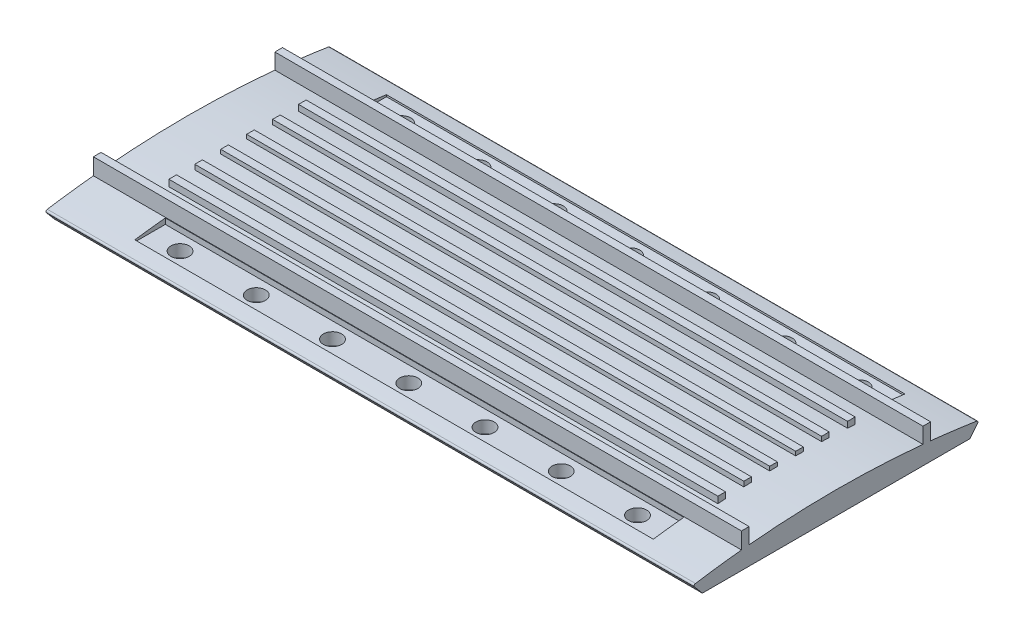
SolidWorks part; units mm, degrees
material "1060 Alloy"
ref_plane "Front Plane" through (0, 0, 0) normal (0, 0, 1) x (1, 0, 0)
ref_plane "Top Plane" through (0, 0, 0) normal (0, 1, 0) x (1, 0, 0)
ref_plane "Right Plane" through (0, 0, 0) normal (1, 0, 0) x (0, 0, -1)
sketch "Sketch1" plane through (0, 0, 0) normal (1, 0, 0) x (0, 0, -1)
  line L0 (-87.6812, 172.5341) -> (-172.5341, 87.6812)
  line L3 (-100, -20) -> (100, -20)
  line L6 (172.5341, 87.6812) -> (87.6812, 172.5341)
  line L10 (0, 0) -> (0, 98.5268) construction
  line L11 (-130.1076, 130.1076) -> (0, 0) construction
  line L12 (0, 0) -> (130.1076, 130.1076) construction
  line L17 (87.6812, 172.5341) -> (-87.6812, 172.5341) construction
  line L18 (172.5341, 87.6812) -> (100, 26.8179)
  line L19 (100, 26.8179) -> (100, -20)
  line L20 (-100, 26.8179) -> (-100, -20)
  line L21 (-172.5341, 87.6812) -> (-100, 26.8179)
  line L22 (-87.6812, 172.5341) -> (-26.8179, 100)
  line L23 (-26.8179, 100) -> (26.8179, 100)
  line L24 (26.8179, 100) -> (87.6812, 172.5341)
  line L25 (-100, 26.8179) -> (-26.8179, 100) construction
  circle A0 centre (0, 0) radius 16
  point P24 (0, 100)
  dimension "D8" = 32
  dimension "D9" = 5
  dimension "D1" = 90
  dimension "D2" = 45
  dimension "D3" = 120
  dimension "D4" = 200
  dimension "D5" = 20
  dimension "D6" = 184
  dimension "D7" = 5
sketch "Sketch2" plane through (0, 0, 0) normal (1, 0, 0) x (0, 0, -1)
  line L0 (-87.6812, 172.5341) -> (-93.9745, 180.0341)
  line L1 (-93.9745, 180.0341) -> (93.9745, 180.0341) construction
  line L2 (93.9745, 180.0341) -> (87.6812, 172.5341)
  line L3 (26.8179, 100) -> (87.6812, 172.5341) construction
  line L4 (87.6812, 172.5341) -> (-87.6812, 172.5341) construction
  line L5 (-87.6812, 172.5341) -> (-26.8179, 100) construction
  line L6 (-87.6812, 172.5341) -> (87.6812, 172.5341)
  arc A0 (-93.9745, 180.0341) -> (93.9745, 180.0341) centre (0, -412.5609) cw
  dimension "D2" = 600
  dimension "D1" = 7.5
extrude "Boss-Extrude1" add sketch "Sketch2" along normal blind 212.5 and the other way blind 212.5
sketch "Sketch3" plane through (0, 0, 0) normal (0, 1, 0) x (1, 0, 0)
  line L0 (-212.5, -87.6812) -> (-212.5, 87.6812) construction
  line L1 (-212.5, 87.6812) -> (212.5, 87.6812) construction
  circle A0 centre (-145, 72.6812) radius 6
  circle A1 centre (-95, 72.6812) radius 6
  circle A2 centre (-45, 72.6812) radius 6
  circle A3 centre (5, 72.6812) radius 6
  circle A4 centre (55, 72.6812) radius 6
  circle A5 centre (105, 72.6812) radius 6
  circle A6 centre (155, 72.6812) radius 6
  dimension "D4" = 50
  dimension "D5" = 50
  dimension "D6" = 50
  dimension "D7" = 50
  dimension "D8" = 50
  dimension "D9" = 12
  dimension "D1" = 67.5
  dimension "D2" = 15
  dimension "D3" = 50
extrude "Cut-Extrude1" cut sketch "Sketch3" along normal through all
mirror "Mirror1" about plane through (0, 0, 0) normal (0, 0, 1) of "Cut-Extrude1"
fillet "Fillet1" radius 1 2 edges at (0, 180.0341, -93.9745) (0, 180.0341, 93.9745)
sketch "Sketch4" plane through (0, 0, 0) normal (1, 0, 0) x (0, 0, -1)
  line L0 (-62, 172.5341) -> (-62, 160.5341)
  line L1 (-87.6812, 172.5341) -> (87.6812, 172.5341) construction
  line L2 (-62, 160.5341) -> (-57, 160.5341)
  line L3 (-57, 160.5341) -> (-57, 172.5341)
  line L4 (0, 0) -> (0, 248.1836) construction
  line L5 (87.6812, 172.5341) -> (-87.6812, 172.5341) construction
  line L6 (-45, 172.5341) -> (-40, 172.5341)
  line L7 (-45, 172.5341) -> (-45, 142.5341)
  line L8 (-45, 142.5341) -> (-40, 142.5341)
  line L9 (-40, 172.5341) -> (-40, 142.5341)
  line L10 (-62, 172.5341) -> (-57, 172.5341)
  line L11 (-28, 172.5341) -> (-23, 172.5341)
  line L12 (-28, 172.5341) -> (-28, 127.5341)
  line L13 (-28, 127.5341) -> (-23, 127.5341)
  line L14 (-23, 172.5341) -> (-23, 127.5341)
  line L15 (-11, 172.5341) -> (-6, 172.5341)
  line L16 (-11, 172.5341) -> (-11, 112.5341)
  line L17 (-11, 112.5341) -> (-6, 112.5341)
  line L18 (-6, 172.5341) -> (-6, 112.5341)
  line L19 (6, 172.5341) -> (6, 112.5341)
  line L20 (11, 112.5341) -> (6, 112.5341)
  line L21 (11, 172.5341) -> (11, 112.5341)
  line L22 (11, 172.5341) -> (6, 172.5341)
  line L23 (23, 172.5341) -> (23, 127.5341)
  line L24 (28, 127.5341) -> (23, 127.5341)
  line L25 (28, 172.5341) -> (28, 127.5341)
  line L26 (28, 172.5341) -> (23, 172.5341)
  line L27 (62, 172.5341) -> (57, 172.5341)
  line L28 (40, 172.5341) -> (40, 142.5341)
  line L29 (45, 142.5341) -> (40, 142.5341)
  line L30 (45, 172.5341) -> (45, 142.5341)
  line L31 (45, 172.5341) -> (40, 172.5341)
  line L32 (57, 160.5341) -> (57, 172.5341)
  line L33 (62, 160.5341) -> (57, 160.5341)
  line L34 (62, 172.5341) -> (62, 160.5341)
  dimension "D1" = 5
  dimension "D2" = 6
  dimension "D3" = 12
  dimension "D4" = 12
  dimension "D5" = 12
  dimension "D6" = 12
  dimension "D7" = 30
  dimension "D8" = 45
  dimension "D9" = 60
extrude "Boss-Extrude2" add sketch "Sketch4" along normal blind 150 and the other way blind 200
sketch "Sketch5" plane through (0, 0, 0) normal (1, 0, 0) x (0, 0, -1)
  line L1 (-62, 180.0341) -> (-57, 180.0341)
  line L2 (-62, 180.0341) -> (-62, 195.0341)
  line L3 (-62, 195.0341) -> (-57, 195.0341)
  line L4 (-57, 180.0341) -> (-57, 195.0341)
  line L5 (-57, 160.5341) -> (-57, 172.5341) construction
  line L6 (57, 180.0341) -> (62, 180.0341)
  line L7 (57, 180.0341) -> (57, 195.0341)
  line L8 (57, 195.0341) -> (62, 195.0341)
  line L9 (62, 180.0341) -> (62, 195.0341)
  line L10 (-62, 172.5341) -> (-62, 160.5341) construction
  line L11 (62, 160.5341) -> (62, 172.5341) construction
  line L12 (57, 172.5341) -> (57, 160.5341) construction
  line L13 (-57, 172.5341) -> (-62, 172.5341) construction
  point P18 (-59.5, 172.5341)
  dimension "D1" = 15
  dimension "D2" = 7.5
extrude "Boss-Extrude3" add sketch "Sketch5" along normal up to surface and the other way up to surface up to face at (212.5, 178.4217, 0) other way up to face at (-212.5, 178.4217, 0)
sketch "Sketch6" plane through (0, 0, 0) normal (1, 0, 0) x (0, 0, -1)
  line L0 (-45, 172.5341) -> (-45, 142.5341) construction
  line L1 (-45, 180.0341) -> (-40, 180.0341)
  line L2 (-45, 180.0341) -> (-45, 190.0341)
  line L3 (-45, 190.0341) -> (-40, 190.0341)
  line L4 (-40, 180.0341) -> (-40, 190.0341)
  line L5 (-28, 180.0341) -> (-23, 180.0341)
  line L6 (-28, 180.0341) -> (-28, 190.0341)
  line L7 (-28, 190.0341) -> (-23, 190.0341)
  line L8 (-23, 180.0341) -> (-23, 190.0341)
  line L9 (-11, 180.0341) -> (-6, 180.0341)
  line L10 (-11, 180.0341) -> (-11, 190.0341)
  line L11 (-11, 190.0341) -> (-6, 190.0341)
  line L12 (-6, 180.0341) -> (-6, 190.0341)
  line L13 (6, 180.0341) -> (11, 180.0341)
  line L14 (6, 180.0341) -> (6, 190.0341)
  line L15 (6, 190.0341) -> (11, 190.0341)
  line L16 (11, 180.0341) -> (11, 190.0341)
  line L17 (23, 180.0341) -> (28, 180.0341)
  line L18 (23, 180.0341) -> (23, 190.0341)
  line L19 (23, 190.0341) -> (28, 190.0341)
  line L20 (28, 180.0341) -> (28, 190.0341)
  line L21 (40, 180.0341) -> (45, 180.0341)
  line L22 (40, 180.0341) -> (40, 190.0341)
  line L23 (40, 190.0341) -> (45, 190.0341)
  line L24 (45, 180.0341) -> (45, 190.0341)
  line L25 (-40, 142.5341) -> (-40, 172.5341) construction
  line L26 (-28, 172.5341) -> (-28, 127.5341) construction
  line L27 (-11, 172.5341) -> (-11, 112.5341) construction
  line L28 (6, 172.5341) -> (6, 112.5341) construction
  line L29 (23, 172.5341) -> (23, 127.5341) construction
  line L30 (40, 172.5341) -> (40, 142.5341) construction
  line L32 (-87.6812, 172.5341) -> (87.6812, 172.5341) construction
  dimension "D1" = 7.5
  dimension "D2" = 10
extrude "Boss-Extrude4" add sketch "Sketch6" along normal blind 180 and the other way blind 180
sketch "Sketch7" plane through (0, 0, 0) normal (1, 0, 0) x (0, 0, -1)
  line L0 (-87.6812, 172.5341) -> (87.6812, 172.5341) construction
  line L1 (-82.3188, 187.5341) -> (-62.3188, 187.5341)
  line L2 (-82.3188, 187.5341) -> (-82.3188, 180.5341)
  line L3 (-82.3188, 180.5341) -> (-62.3188, 180.5341)
  line L4 (-62.3188, 187.5341) -> (-62.3188, 180.5341)
  line L5 (62.6812, 187.5341) -> (82.6812, 187.5341)
  line L6 (62.6812, 187.5341) -> (62.6812, 180.5341)
  line L7 (62.6812, 180.5341) -> (82.6812, 180.5341)
  line L8 (82.6812, 187.5341) -> (82.6812, 180.5341)
  point P8 (72.6812, 180.5341)
  point P12 (-72.3188, 180.5341)
  dimension "D1" = 20
  dimension "D2" = 8
  dimension "D3" = 145
  dimension "D4" = 7
extrude "Cut-Extrude2" cut sketch "Sketch7" against normal blind 165 and the other way blind 175
